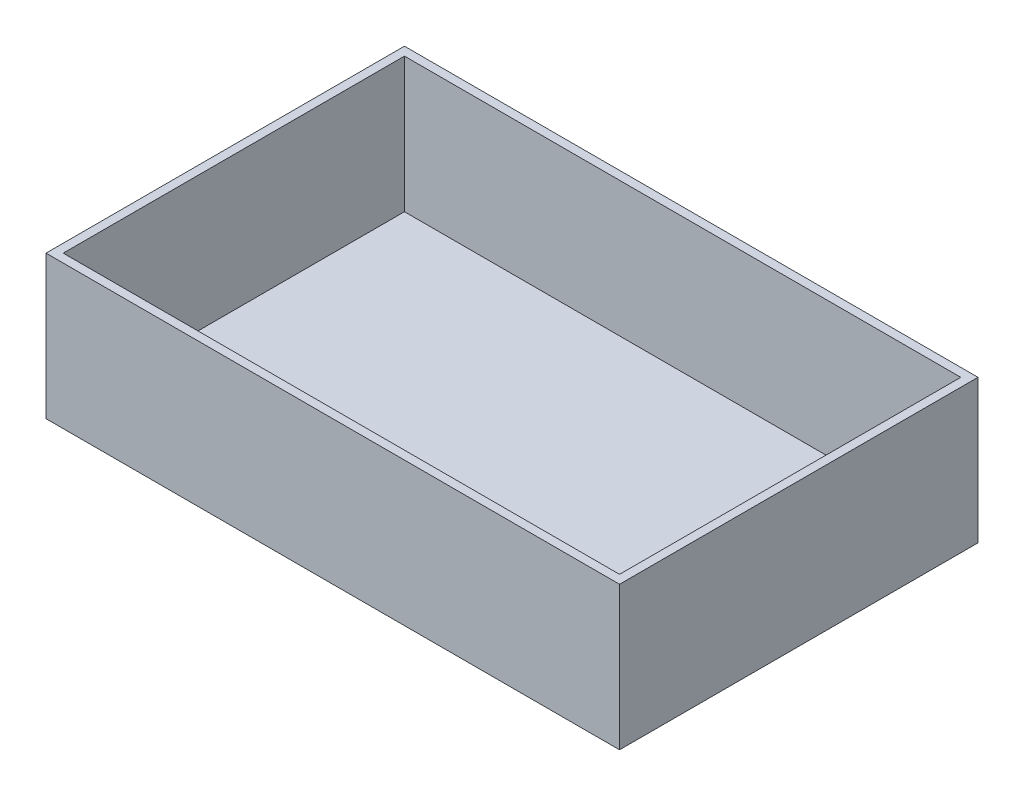
SolidWorks part; units mm, degrees
ref_plane "Front Plane" through (0, 0, 0) normal (0, 0, 1) x (1, 0, 0)
ref_plane "Top Plane" through (0, 0, 0) normal (0, 1, 0) x (1, 0, 0)
ref_plane "Right Plane" through (0, 0, 0) normal (1, 0, 0) x (0, 0, -1)
sketch "Sketch1" plane through (0, 0, 0) normal (0, 1, 0) x (1, 0, 0)
  line L1 (-200, 125) -> (200, 125)
  line L2 (-200, 125) -> (-200, -125)
  line L3 (-200, -125) -> (200, -125)
  line L4 (200, 125) -> (200, -125)
  line L5 (-200, 125) -> (200, -125) construction
  line L6 (-200, -125) -> (200, 125) construction
  line L7 (-194, 119) -> (194, 119)
  line L8 (-194, 119) -> (-194, -119)
  line L9 (-194, -119) -> (194, -119)
  line L10 (194, 119) -> (194, -119)
  line L11 (-194, 119) -> (194, -119) construction
  line L12 (-194, -119) -> (194, 119) construction
  point P0 (0, 0)
  point P6 (0, 0)
  point P11 (0, 0)
  point P12 (0, 0)
  point P13 (0, 0)
  point P14 (0, 0)
  point P15 (0, 0)
  point P16 (0, 0)
  point P17 (0, 0)
  point P18 (0, 0)
  point P19 (0, 0)
  point P20 (0, 0)
  point P21 (0, 0)
  dimension "D1" = 400
  dimension "D2" = 250
  dimension "D3" = 388
  dimension "D4" = 238
extrude "Boss-Extrude1" add sketch "Sketch1" along normal blind 6 contours L10 L7 L8 L9 region at (0, 0, 0)
extrude "Boss-Extrude2" add sketch "Sketch1<3>" along normal blind 100
sketch "Sketch1<3>" plane through (0, 0, 0) normal (0, 1, 0) x (1, 0, 0) same geometry as "Sketch1"
equation "\"Battery_Case_Width\"= 40cm"
equation "\"Battery_Case_Length\"= 25cm"
equation "\"Battery_Case_Thickness\" = 6mm"
equation "\"Battery_Case_Height\"= 10cm"
equation "\"D1@Sketch1\"=\"Battery_Case_Width\""
equation "\"D2@Sketch1\"=\"Battery_Case_Length\""
equation "\"D4@Sketch1\"=\"Battery_Case_Length\"-2*\"Battery_Case_Thickness\""
equation "\"D3@Sketch1\"=\"Battery_Case_Width\"-2*\"Battery_Case_Thickness\""
equation "\"D1@Boss-Extrude1\"=\"Battery_Case_Thickness\""
equation "\"D1@Boss-Extrude2\"=\"Battery_Case_Height\""
